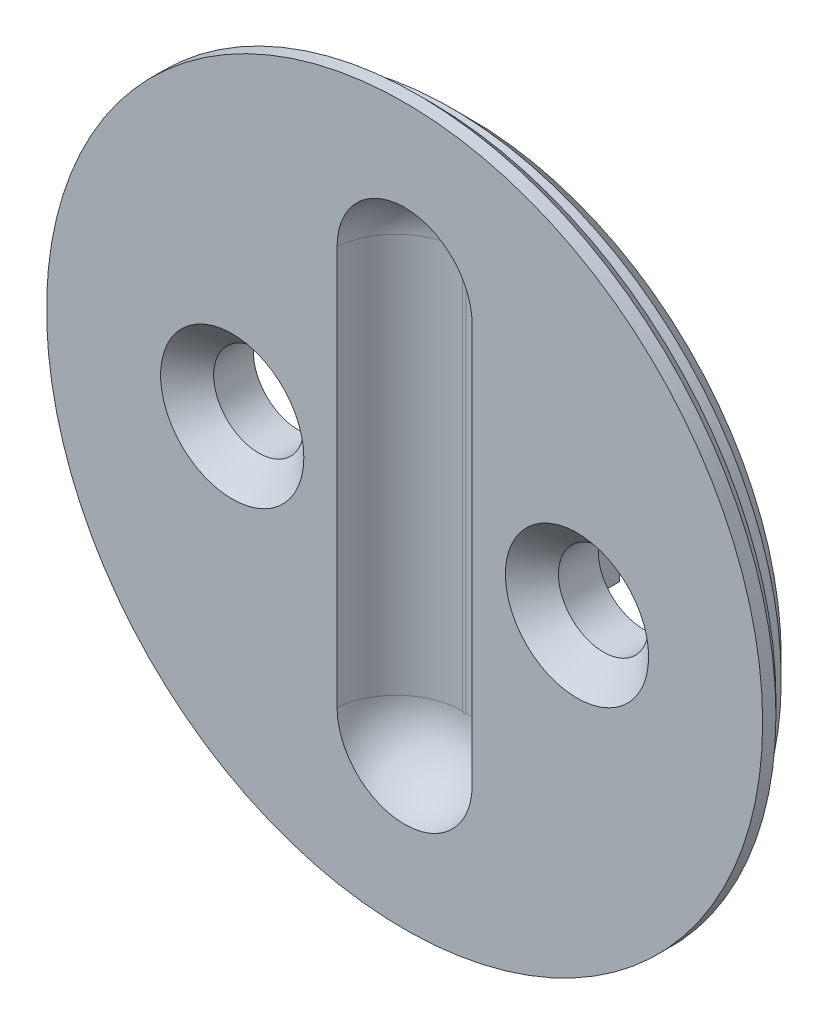
SolidWorks part; units mm, degrees
ref_plane "Front Plane" through (0, 0, 0) normal (0, 0, 1) x (1, 0, 0)
ref_plane "Top Plane" through (0, 0, 0) normal (0, 1, 0) x (1, 0, 0)
ref_plane "Right Plane" through (0, 0, 0) normal (1, 0, 0) x (0, 0, -1)
sketch "Sketch1" plane through (0, 0, 0) normal (0, 0, 1) x (1, 0, 0)
  line L0 (0, 9.3188) -> (0, -6.9028) construction
  circle A0 centre (0, 0) radius 12.45
  circle A1 centre (-6.5, 0) radius 1.7
  circle A2 centre (6.5, 0) radius 1.7
  dimension "D2" = 24.9
  dimension "D3" = 3.4
  dimension "D1" = 13
extrude "Boss-Extrude1" add sketch "Sketch1" against normal blind 1.5
sketch "Sketch2" plane through (0, 0, -1.5) normal (0, 0, -1) x (-1, 0, 0)
  line L1 (-2.85, 3.35) -> (2.85, 3.35)
  line L2 (-2.85, 3.35) -> (-2.85, -3.35)
  line L3 (-2.85, -3.35) -> (2.85, -3.35)
  line L4 (2.85, 3.35) -> (2.85, -3.35)
  line L5 (-2.85, 3.35) -> (2.85, -3.35) construction
  line L6 (-2.85, -3.35) -> (2.85, 3.35) construction
  point P0 (0, 0)
  dimension "D1" = 6.7
  dimension "D2" = 5.7
extrude "Boss-Extrude2" add sketch "Sketch2" along normal blind 3.5
sketch "Sketch3" plane through (0, 0, 0) normal (0, 0, 1) x (1, 0, 0)
  circle A0 centre (0, 0) radius 13.5
  circle A1 centre (-6.5, 0) radius 1.7
  circle A2 centre (6.5, 0) radius 1.7
  circle A3 centre (-6.5, 0) radius 1.7 construction
  dimension "D1" = 27
extrude "Boss-Extrude3" add sketch "Sketch3" along normal blind 1
chamfer "Chamfer1" distance 0.75 angle 45 5 edges at (0, 3.35, -5) (2.85, 0, -5) (0, -3.35, -5) (-2.85, 0, -5) (12.45, 0, -1.5)
chamfer "Chamfer2" distance 0.5 angle 45 1 edges at (13.5, 0, 0)
sketch "Sketch4" plane through (0, 0, 1) normal (0, 0, 1) x (1, 0, 0)
  line L0 (0, 7.5257) -> (0, -7.5257) construction
  line L1 (2.5463, 7.5257) -> (2.5463, -7.5257)
  line L2 (-2.5463, 7.5257) -> (-2.5463, -7.5257)
  arc A0 (2.5463, 7.5257) -> (-2.5463, 7.5257) centre (0, 7.5257) ccw
  arc A1 (-2.5463, -7.5257) -> (2.5463, -7.5257) centre (0, -7.5257) ccw
  point P2 (0, 0)
extrude "Cut-Extrude1" cut sketch "Sketch4" against normal blind 2.25
fillet "Fillet1" radius 2.5 4 edges at (-2.5463, 0, -1.25) (2.5463, 0, -1.25) (0, 10.0719, -1.25) (0, -10.0719, -1.25)
chamfer "Chamfer3" distance 1 angle 45 2 edges at (8.2, 0, 1) (-4.8, 0, 1)
